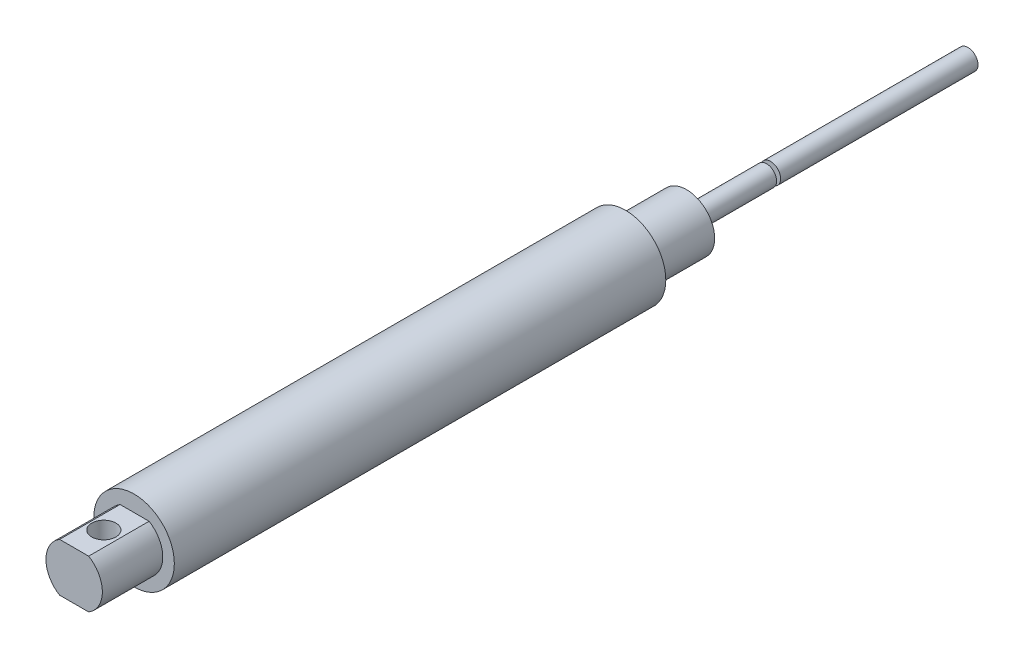
SolidWorks part; units mm, degrees
ref_plane "前视基准面" through (0, 0, 0) normal (0, 0, 1) x (1, 0, 0)
ref_plane "上视基准面" through (0, 0, 0) normal (0, 1, 0) x (1, 0, 0)
ref_plane "右视基准面" through (0, 0, 0) normal (1, 0, 0) x (0, 0, -1)
sketch "草图1" plane through (0, 0, 0) normal (0, 0, 1) x (1, 0, 0)
  circle A0 centre (0, 0) radius 10
  dimension "D1" = 20
extrude "凸台-拉伸1" add sketch "草图1" along normal blind 152
sketch "草图2" plane through (0, 0, 152) normal (0, 0, 1) x (1, 0, 0)
  line L0 (-3.4745, 6) -> (3.7367, 6)
  line L1 (-3.4745, -6) -> (3.7367, -6)
  circle A0 centre (0.1311, 0) radius 7
  circle A2 centre (0, 0) radius 10
  circle A3 centre (0, 0) radius 10
  circle M1 centre (0, 0) radius 10
  dimension "D1" = 14
  dimension "D2" = 12
  dimension "D3" = 0
extrude "切除-拉伸1" cut sketch "草图2" against normal blind 15 contours L0 A0 | L1 A0 | A0 M1 region at (0.1311, 6.4026, 152) region at (0.1311, -6.4026, 152) region at (-9.7172, 0, 152)
extrude "切除-拉伸2" cut sketch "草图2<3>" along normal blind 15 from surface contours A0 M1 region at (-9.7172, 0, 152) starting at face at (10, 0, 0)
sketch "草图2<3>" plane through (0, 0, 152) normal (0, 0, 1) x (1, 0, 0) same geometry as "草图2"
sketch "草图3" plane through (0, 6, 0) normal (0, 1, 0) x (1, 0, 0)
  circle A0 centre (0, -144.5) radius 3
  dimension "D1" = 6
extrude "切除-拉伸3" cut sketch "草图3" against normal through all
sketch "草图4" plane through (0, 0, 0) normal (0, 0, -1) x (-1, 0, 0)
  circle A0 centre (0, 0) radius 2.5
  dimension "D1" = 5
extrude "凸台-拉伸2" add sketch "草图4" along normal blind 20
extrude "凸台-拉伸3" add sketch "草图4<2>" along normal blind 49 from offset 21 separate body
sketch "草图4<2>" plane through (0, 0, 0) normal (0, 0, -1) x (-1, 0, 0) same geometry as "草图4"
